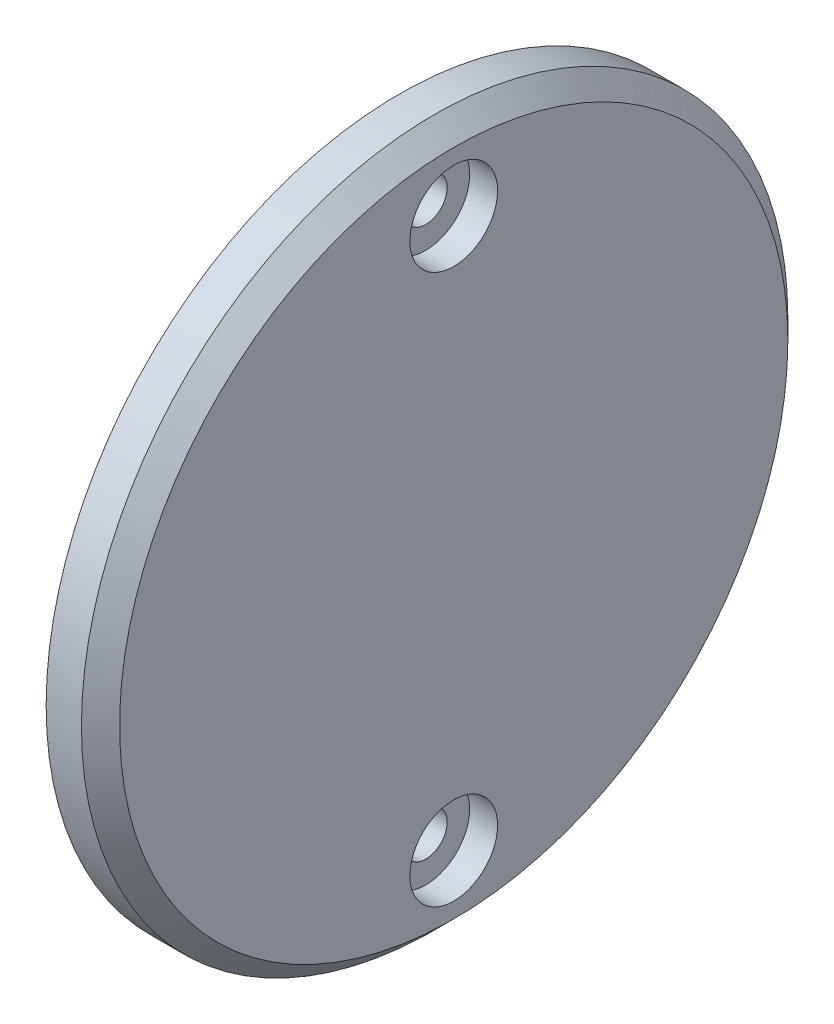
SolidWorks part; units mm, degrees
material "SideBearingAttachPlate"
ref_plane "Front Plane" through (0, 0, 0) normal (0, 0, 1) x (1, 0, 0)
ref_plane "Top Plane" through (0, 0, 0) normal (0, 1, 0) x (1, 0, 0)
ref_plane "Right Plane" through (0, 0, 0) normal (1, 0, 0) x (0, 0, -1)
sketch "Sketch1" plane through (0, 0, 0) normal (1, 0, 0) x (0, 0, -1)
  circle A0 centre (0, 0) radius 55.5625
  dimension "D1" = 111.125
extrude "Boss-Extrude1" add sketch "Sketch1" along normal blind 8.55
chamfer "Chamfer1" distance 3 angle 45 1 edges at (8.55, 0, -55.5625)
sketch "Sketch3" plane through (8.55, 0, 0) normal (1, 0, 0) x (0, 0, -1)
  line L0 (0, -43.225) -> (0, 43.225)
  circle A0 centre (0, 43.225) radius 6.9
  circle A1 centre (0, -43.225) radius 6.9
  point P9 (0, 0)
  dimension "D1" = 13.8
  dimension "D2" = 13.8
  dimension "D3" = 86.45
extrude "Cut-Extrude1" cut sketch "Sketch3" against normal blind 4.4 contours A1 | A0 region at (8.55, 47.966, 4.741) region at (8.55, -38.484, -4.741)
sketch "Sketch4" plane through (4.15, 0, 0) normal (1, 0, 0) x (0, 0, -1)
  circle A0 centre (0, 43.225) radius 3.375
  circle A1 centre (0, -43.225) radius 3.375
  dimension "D1" = 6.75
  dimension "D2" = 6.75
extrude "Cut-Extrude2" cut sketch "Sketch4" against normal up to surface (4.15 mm away) up to face at (0, 0, -55.5625)
sketch "AssemblyConstruction" plane through (0, 0, 0) normal (-1, 0, 0) x (0, 0, 1)
  line L0 (0, 43.225) -> (0, -43.225) construction
